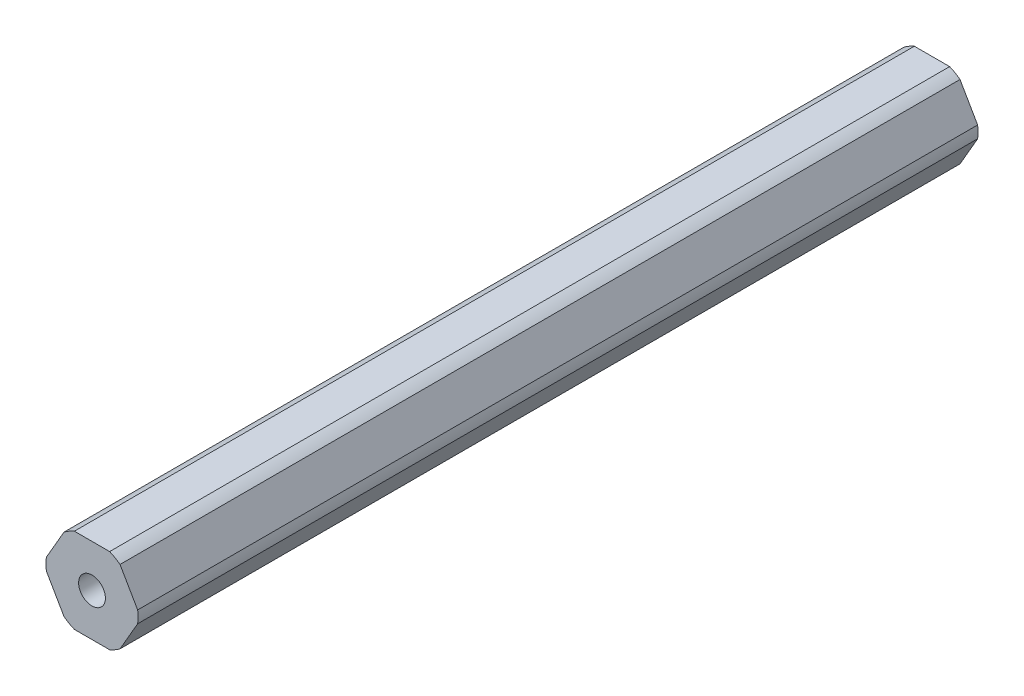
SolidWorks part; units mm, degrees
material "6061-T6 (SS)"
ref_plane "Front Plane" through (0, 0, 0) normal (0, 0, 1) x (1, 0, 0)
ref_plane "Top Plane" through (0, 0, 0) normal (0, 1, 0) x (1, 0, 0)
ref_plane "Right Plane" through (0, 0, 0) normal (1, 0, 0) x (0, 0, -1)
sketch "Sketch1" plane through (0, 0, 0) normal (0, 0, 1) x (1, 0, 0)
  line L1 (3.6662, 6.35) -> (-3.6662, 6.35)
  line L2 (-3.6662, 6.35) -> (-7.3323, 0)
  line L3 (-7.3323, 0) -> (-3.6662, -6.35)
  line L4 (-3.6662, -6.35) -> (3.6662, -6.35)
  line L5 (3.6662, -6.35) -> (7.3323, 0)
  line L6 (7.3323, 0) -> (3.6662, 6.35)
  circle A0 centre (0, 0) radius 6.35 construction
  circle A1 centre (0, 0) radius 2
  circle A2 centre (0, 0) radius 6.875
  point P1 (0, 6.35)
  dimension "D2" = 13.75
  dimension "D3" = 4
  dimension "D1" = 12.7
extrude "Boss-Extrude1" add sketch "Sketch1" along normal mid plane 125.4125 contours L6 A2 L1 L2 L3 L4 L5 A1 region at (3.3439, 5.7918, 0)
sketch "Sketch4" plane through (0, 0, 62.7062) normal (0, 0, 1) x (1, 0, 0)
  circle A0 centre (0, 0) radius 6.35
  circle A2 centre (0, 0) radius 2.4892
  dimension "D1" = 12.7
  dimension "D2" = 4.9784
equation "\"D2@Sketch1\"=13.75mm"
equation "\"D3@Sketch1\"=4mm"
